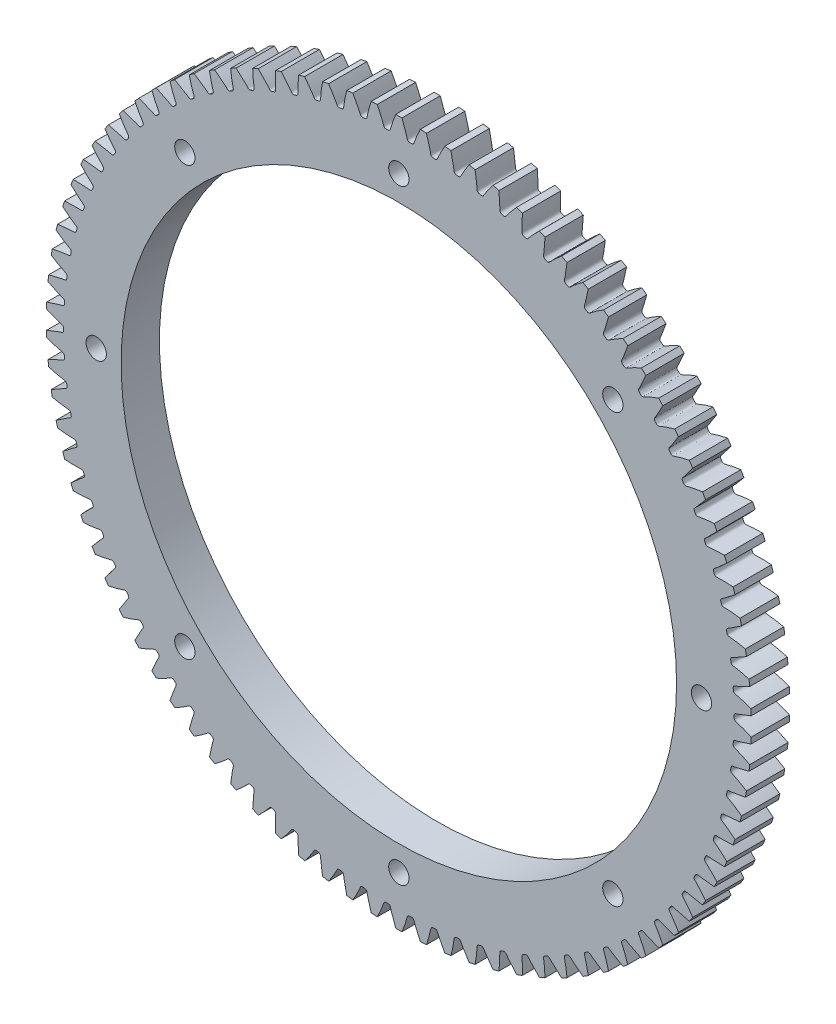
SolidWorks part; units mm, degrees
ref_plane "前视基准面" through (0, 0, 0) normal (0, 0, 1) x (1, 0, 0)
ref_plane "上视基准面" through (0, 0, 0) normal (0, 1, 0) x (1, 0, 0)
ref_plane "右视基准面" through (0, 0, 0) normal (1, 0, 0) x (0, 0, -1)
other "Configuration Table"
ref_axis "基准轴1" through (0, 0, 55) along (0, 0, -1)
sketch "SketchRevolveSpurGear2" plane through (0, 0, 0) normal (1, 0, 0) x (0, 0, -1)
  line L0 (0, 0) -> (1, 0) construction
  line L1 (-5, 0) -> (-5, 92)
  line L2 (-5, 92) -> (5, 92)
  line L3 (5, 92) -> (5, 0)
  line L4 (5, 0) -> (-5, 0)
revolve "SpurGear2" add sketch "SketchRevolveSpurGear2" angle 360 about L0
sketch "SketchToothSpurGear2" plane through (0, 0, 0) normal (0, 0, 1) x (1, 0, 0)
  arc A0 (91.9685, 2.4076) -> (91.9685, -2.4076) centre (0, 0) cw
  spline S0 degree 3 poles (91.9685, -2.4076) (91.7384, -2.3019) (91.4327, -2.1653) (91.0515, -2.0015) (90.8301, -1.9083) (90.612, -1.8183) (90.3974, -1.7316) (90.1862, -1.648) (89.9784, -1.5674) (89.7742, -1.4899) (89.5735, -1.4154) (89.3763, -1.3438) (89.1828, -1.2751) (88.9928, -1.2092) (88.8065, -1.1461) (88.624, -1.0856) (88.445, -1.0281) (88.2119, -0.9533) (88.0055, -0.8975) (87.832, -0.8334) (87.75, -0.7835) (87.6766, -0.7221) (87.6139, -0.6496) (87.5635, -0.5681) (87.5267, -0.4796) (87.5039, -0.3864) (87.4976, -0.2742) (87.5006, -0.1455) (87.4997, 0) (87.5006, 0.1455) (87.4976, 0.2742) (87.5039, 0.3864) (87.5267, 0.4796) (87.5635, 0.5681) (87.6139, 0.6496) (87.6766, 0.7221) (87.75, 0.7835) (87.832, 0.8334) (88.0055, 0.8975) (88.2119, 0.9533) (88.445, 1.0281) (88.624, 1.0856) (88.8065, 1.1461) (88.9928, 1.2092) (89.1828, 1.2751) (89.3763, 1.3438) (89.5735, 1.4154) (89.7742, 1.4899) (89.9784, 1.5674) (90.1862, 1.648) (90.3974, 1.7316) (90.612, 1.8183) (90.8301, 1.9083) (91.0515, 2.0015) (91.4327, 2.1653) (91.7384, 2.3019) (91.9685, 2.4076) knots 0 0 0 0 0.070509 0.093204 0.115496 0.137383 0.158867 0.179946 0.200622 0.220894 0.240762 0.260226 0.279286 0.297942 0.316195 0.334043 0.351488 0.368528 0.402166 0.411021 0.419877 0.428732 0.437587 0.446442 0.455297 0.464153 0.473008 0.486504 0.5 0.513496 0.526992 0.535847 0.544703 0.553558 0.562413 0.571268 0.580123 0.588979 0.597834 0.631472 0.648512 0.665957 0.683805 0.702058 0.720714 0.739774 0.759238 0.779106 0.799378 0.820054 0.841133 0.862617 0.884504 0.906796 0.929491 1 1 1 1
extrude "ToothExtrudeCutSpurGear2" cut sketch "SketchToothSpurGear2" against normal blind 5 and the other way blind 5
pattern_circular "PatternSpurGear2" count 90 every 4 about axis through (0, 0, 55) along (0, 0, -1) of "ToothExtrudeCutSpurGear2"
sketch "BoreRevolveSketch" plane through (0, 0, 0) normal (1, 0, 0) x (0, 0, -1)
  line L0 (0, 0) -> (1, 0) construction
  line L1 (-5, 0) -> (5, 0)
  line L2 (5, 0) -> (5, 5)
  line L3 (5, 5) -> (-5, 5)
  line L4 (-5, 5) -> (-5, 0)
  dimension "TaperSide1" = 5
  dimension "TaperSide2" = 5
revolve "BoreRevolveCut" cut sketch "BoreRevolveSketch" angle 360 about L0
sketch "AuxiliarySketchSpurGear2" plane through (0, 0, 0) normal (0, 0, 1) x (1, 0, 0)
  circle A0 centre (0, 0) radius 90 construction
  circle A1 centre (0, 0) radius 84.5723 construction
  circle A2 centre (0, 0) radius 88.0849 construction
  circle A3 centre (0, 0) radius 92 construction
  circle A4 centre (0, 0) radius 87.5 construction
  dimension "PitchDiameter" = 180
  dimension "BaseDiameter" = 169.1447
  dimension "FormDiameter" = 176.1698
  dimension "MajorDiameter" = 184
  dimension "MinorDiameter" = 175
sketch "草图5" plane through (0, 0, 5) normal (0, 0, 1) x (1, 0, 0)
  circle A0 centre (0, 0) radius 72.5
  circle A2 centre (0, 79) radius 2.65
  circle A3 centre (55.8614, 55.8614) radius 2.65
  circle A4 centre (79, 0) radius 2.65
  circle A5 centre (55.8614, -55.8614) radius 2.65
  circle A6 centre (0, -79) radius 2.65
  circle A7 centre (-55.8614, -55.8614) radius 2.65
  circle A8 centre (-79, 0) radius 2.65
  circle A9 centre (-55.8614, 55.8614) radius 2.65
  point P25 (0, 0)
  dimension "D1" = 145
  dimension "D3" = 5.3
  dimension "D4" = 8
extrude "切除-拉伸3" cut sketch "草图5" against normal blind 10
